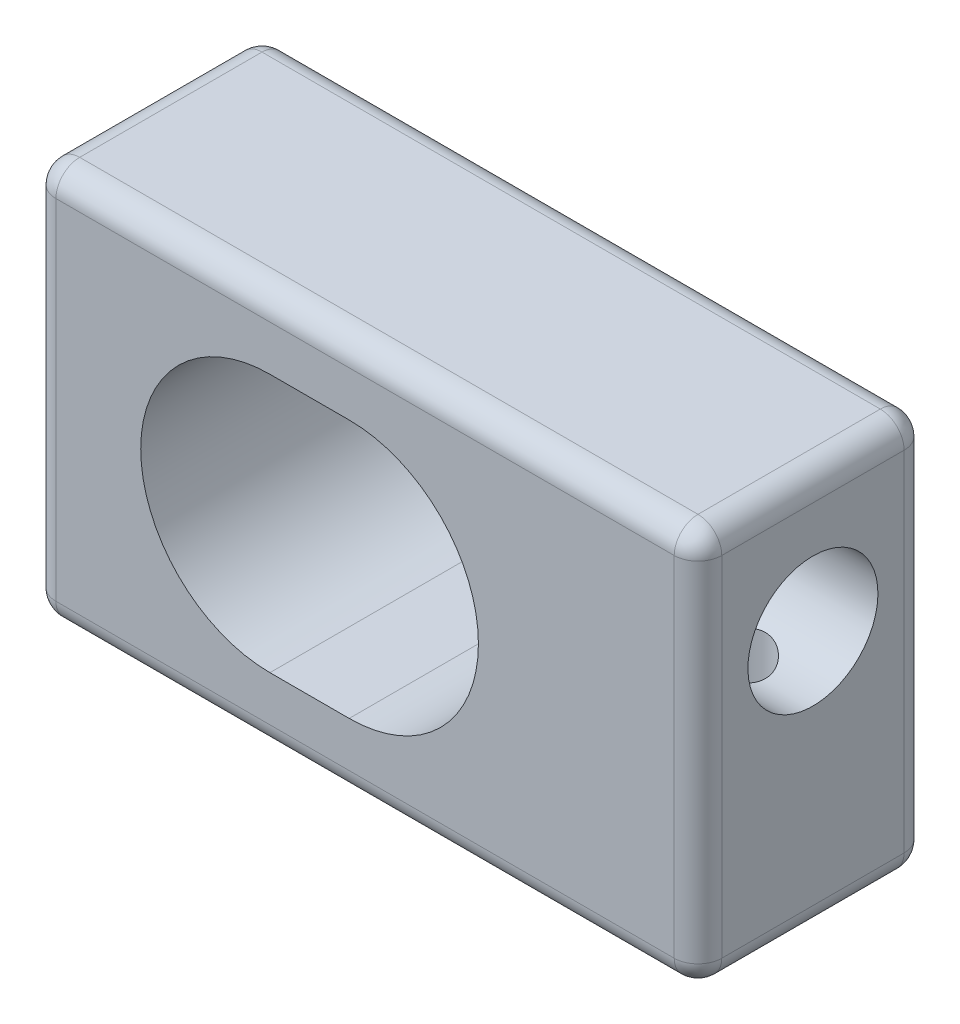
SolidWorks part; units mm, degrees
ref_plane "Front Plane" through (0, 0, 0) normal (0, 0, 1) x (1, 0, 0)
ref_plane "Top Plane" through (0, 0, 0) normal (0, 1, 0) x (1, 0, 0)
ref_plane "Right Plane" through (0, 0, 0) normal (1, 0, 0) x (0, 0, -1)
sketch "Sketch1" plane through (0, 0, 0) normal (0, 0, 1) x (1, 0, 0)
  line L0 (-45, 0) -> (-50, 0) construction
  line L1 (-45, -8.15) -> (-50, -8.15)
  line L2 (-45, 8.15) -> (-50, 8.15)
  line L4 (-65, 12.5) -> (-23, 12.5)
  line L5 (-65, 12.5) -> (-65, -12.5)
  line L6 (-65, -12.5) -> (-23, -12.5)
  line L7 (-23, 12.5) -> (-23, -12.5)
  circle A0 centre (-45, 0) radius 8 construction
  circle A1 centre (-45, 0) radius 6 construction
  arc A2 (-45, -8.15) -> (-45, 8.15) centre (-45, 0) ccw
  arc A3 (-50, 8.15) -> (-50, -8.15) centre (-50, 0) ccw
  point P3 (-47.5, 0)
  dimension "D1" = 16
  dimension "D2" = 12
  dimension "D3" = 45
  dimension "D4" = 16.3
  dimension "D5" = 5
  dimension "D6" = 25
  dimension "D8" = 20
  dimension "D9" = 22
  dimension "D10" = 12.5
  dimension "D12" = 23
extrude "Boss-Extrude1" add sketch "Sketch1" along normal blind 7.25 and the other way blind 7.25
sketch "Sketch2" plane through (-23, 0, 0) normal (1, 0, 0) x (0, 0, -1)
  circle A0 centre (0, 4) radius 4.1
  dimension "D1" = 8.2
  dimension "D2" = 4
extrude "Cut-Extrude1" cut sketch "Sketch2" against normal blind 12
sketch "Sketch3" plane through (0, -12.5, 0) normal (0, 1, 0) x (1, 0, 0)
  line L0 (-23, 7.25) -> (-23, -7.25) construction
  circle A0 centre (-28, 0) radius 2
  dimension "D1" = 4
  dimension "D2" = 5
extrude "Cut-Extrude5" cut sketch "Sketch3" along normal blind 15
fillet "Fillet3" radius 1.5 12 edges at (-65, 0, -7.25) (-65, 12.5, 0) (-65, 0, 7.25) (-65, -12.5, 0) (-23, 0, 7.25) (-23, 0, -7.25) (-44, -12.5, -7.25) (-44, -12.5, 7.25) (-44, 12.5, 7.25) (-23, -12.5, 0) (-23, 12.5, 0) (-44, 12.5, -7.25)
